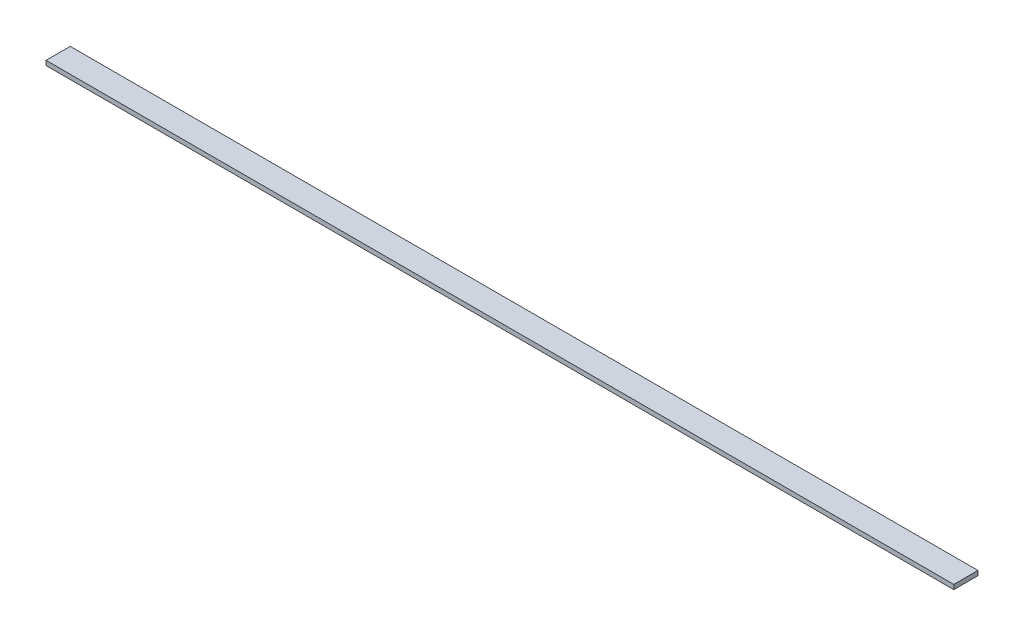
SolidWorks part; units mm, degrees
ref_plane "Vorne" through (0, 0, 0) normal (0, 0, 1) x (1, 0, 0)
ref_plane "Oben" through (0, 0, 0) normal (0, 1, 0) x (1, 0, 0)
ref_plane "Rechts" through (0, 0, 0) normal (1, 0, 0) x (0, 0, -1)
ref_plane "E_Boden" through (0, 1, 0) normal (0, 1, 0) x (1, 0, 0)
sketch "Skizze1" plane through (0, 0, 0) normal (0, 1, 0) x (1, 0, 0)
  line L0 (0, 0) -> (-118.8274, 0) construction
  line L1 (-118.8274, 0) -> (167.8176, 0) construction
  line L2 (0, 0) -> (0, 71.7915) construction
  line L3 (0, 71.7915) -> (0, -82.215) construction
  line L5 (-750, 20) -> (750, 20)
  line L6 (-750, 20) -> (-750, -20)
  line L7 (-750, -20) -> (750, -20)
  line L8 (750, 20) -> (750, -20)
  dimension "D1" = 40
  dimension "D2" = 1500
extrude "Aufsatz-Linear austragen1" add sketch "Skizze1" along normal blind 7.5
